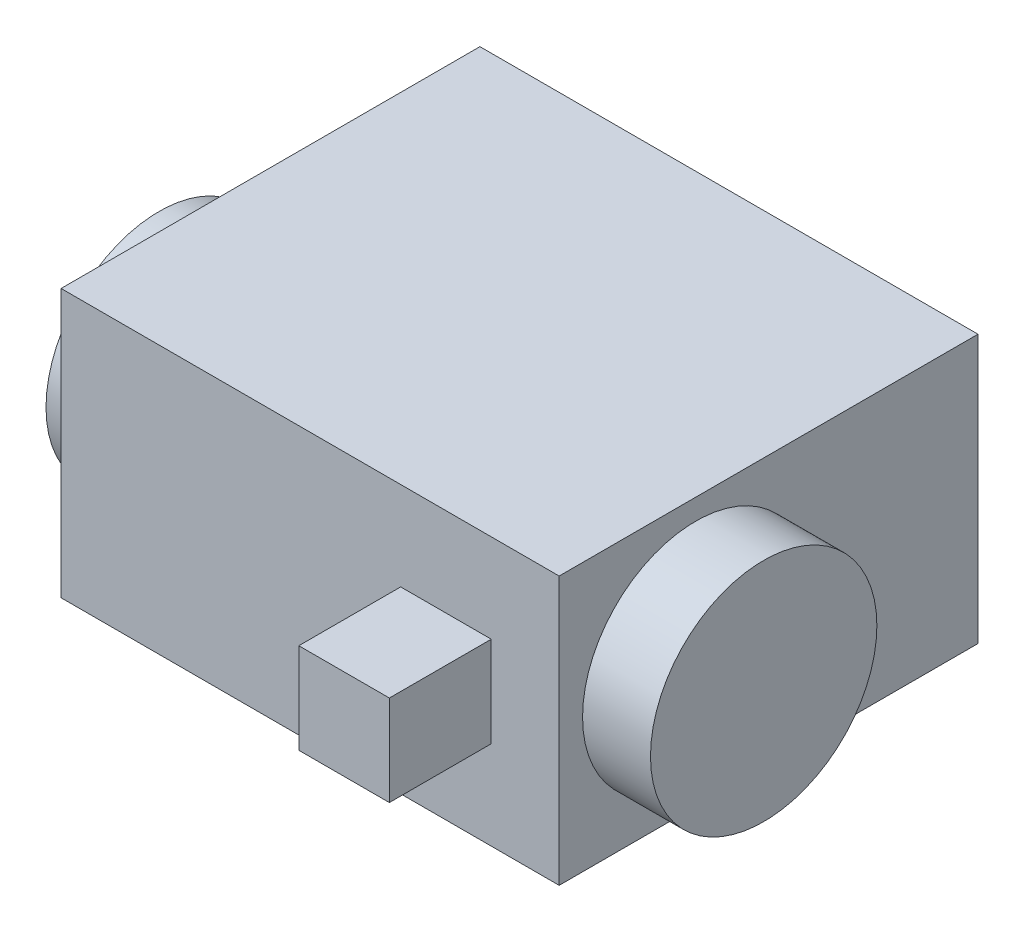
SolidWorks part; units mm, degrees
material "未指定"
ref_plane "正面" through (0, 0, 0) normal (0, 0, 1) x (1, 0, 0)
ref_plane "平面" through (0, 0, 0) normal (0, 1, 0) x (1, 0, 0)
ref_plane "右側面" through (0, 0, 0) normal (1, 0, 0) x (0, 0, -1)
sketch "ｽｹｯﾁ1" plane through (0, 0, 0) normal (1, 0, 0) x (0, 0, -1)
  line L0 (37.4, -17.75) -> (-18.1, -17.75)
  line L1 (-18.1, -17.75) -> (-18.1, 17.75)
  line L2 (-18.1, 17.75) -> (37.4, 17.75)
  line L3 (37.4, 17.75) -> (37.4, -17.75)
  line L4 (0, 0) -> (-25, 0) construction
  dimension "D1" = 18.1
  dimension "D2" = 37.4
  dimension "D3" = 35.5
extrude "本体" add sketch "ｽｹｯﾁ1" along normal mid plane 66
sketch "ｽｹｯﾁ2" plane through (0, 0, 0) normal (0, 0, 1) x (1, 0, 0)
  line L0 (0, 0) -> (47, 0) construction
  line L1 (33, 0) -> (42, 0)
  line L2 (42, 0) -> (42, 15)
  line L3 (42, 15) -> (33, 15)
  line L4 (33, 15) -> (33, 0)
  dimension "D1" = 42
  dimension "D2" = 33
  dimension "D3" = 15
revolve "出力円板" add sketch "ｽｹｯﾁ2" angle 360 about L0
sketch "ｽｹｯﾁ3" plane through (0, 0, 0) normal (0, 0, 1) x (1, 0, 0)
  line L0 (0, 0) -> (47, 0) construction
  line L1 (-38.1, 0) -> (-33, 0)
  line L2 (-33, 0) -> (-33, 15)
  line L3 (-33, 15) -> (-38.1, 15)
  line L4 (-38.1, 15) -> (-38.1, 0)
  dimension "D1" = 33
  dimension "D2" = 38.1
  dimension "D3" = 15
revolve "従動軸" add sketch "ｽｹｯﾁ3" angle 360 about L0
sketch "ｽｹｯﾁ4" plane through (0, 0, 0) normal (0, 0, 1) x (1, 0, 0)
  line L0 (12, -6) -> (24, -6)
  line L1 (24, -6) -> (24, 6)
  line L2 (24, 6) -> (12, 6)
  line L3 (12, 6) -> (12, -6)
  line L4 (0, 0) -> (25, 0) construction
  dimension "D1" = 24
  dimension "D2" = 12
  dimension "D3" = 12
extrude "ケーブルグランド" add sketch "ｽｹｯﾁ4" along normal mid plane 63.2
ref_axis "中心軸" through (-42.105, 0, 0) along (1, 0, 0)
equation "\"SERVO_AX_TOP\" = 18.1"
equation "\"D1@ｽｹｯﾁ1\" = \"SERVO_AX_TOP\""
equation "\"SERVO_AX_BOTTOM\" = 37.4"
equation "\"D2@ｽｹｯﾁ1\" = \"SERVO_AX_BOTTOM\""
equation "\"SERVO_W\" = 35.5"
equation "\"D3@ｽｹｯﾁ1\" = \"SERVO_W\""
equation "\"SERVO_BODY_L\" = 66"
equation "\"D1@本体\" = \"SERVO_BODY_L\""
equation "\"SERVO_DISC_T\" = 9"
equation "\"D1@ｽｹｯﾁ2\" = \"SERVO_BODY_L\" / 2 + \"SERVO_DISC_T\""
equation "\"D2@ｽｹｯﾁ2\" = \"SERVO_BODY_L\" / 2"
equation "\"SERVO_DISC_D\" = 30"
equation "\"D3@ｽｹｯﾁ2\" = \"SERVO_DISC_D\" / 2"
equation "\"D1@ｽｹｯﾁ3\" = \"SERVO_BODY_L\" / 2"
equation "\"SERVO_IDLER_T\" = 5.1"
equation "\"D2@ｽｹｯﾁ3\" = abs( -\"SERVO_BODY_L\" / 2 - \"SERVO_IDLER_T\" )"
equation "\"D3@ｽｹｯﾁ3\" = \"SERVO_DISC_D\" / 2"
equation "\"SERVO_GLAND_POS\" = 18"
equation "\"SERVO_GLAND_D\" = 12"
equation "\"D1@ｽｹｯﾁ4\" = \"SERVO_GLAND_POS\" + \"SERVO_GLAND_D\" / 2"
equation "\"D2@ｽｹｯﾁ4\" = \"SERVO_GLAND_POS\" - \"SERVO_GLAND_D\" / 2"
equation "\"D3@ｽｹｯﾁ4\" = \"SERVO_GLAND_D\""
equation "\"SERVO_GLAND_SPAN\" = 63.2"
equation "\"D1@ケーブルグランド\" = \"SERVO_GLAND_SPAN\""
